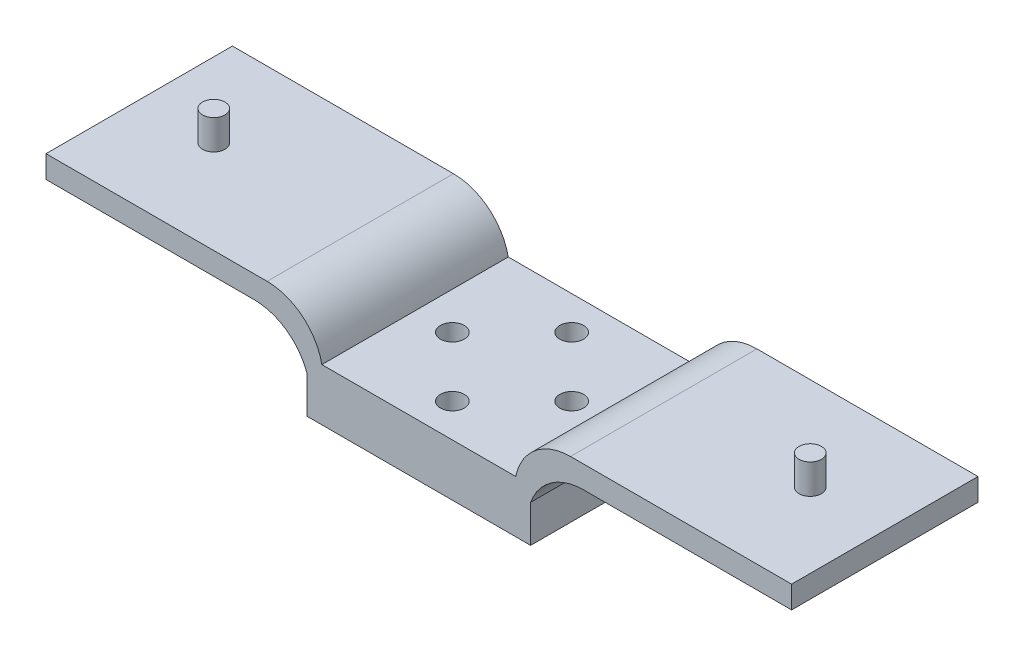
SolidWorks part; units mm, degrees
ref_plane "前视基准面" through (0, 0, 0) normal (0, 0, 1) x (1, 0, 0)
ref_plane "上视基准面" through (0, 0, 0) normal (0, 1, 0) x (1, 0, 0)
ref_plane "右视基准面" through (0, 0, 0) normal (1, 0, 0) x (0, 0, -1)
sketch "Sketch1" plane through (0, 0, 0) normal (0, 1, 0) x (1, 0, 0)
  line L1 (-50, 12.5) -> (50, 12.5)
  line L2 (-50, 12.5) -> (-50, -12.5)
  line L3 (-50, -12.5) -> (50, -12.5)
  line L4 (50, 12.5) -> (50, -12.5)
  line L5 (0, -12.5) -> (0, 12.5) construction
  line L6 (-50, 0) -> (50, 0) construction
  point P0 (0, 0)
  dimension "D1" = 100
  dimension "D2" = 25
extrude "Boss-Extrude1" add sketch "Sketch1" along normal blind 3
sketch "Sketch2" plane through (0, 0, 0) normal (0, -1, 0) x (1, 0, 0)
  line L0 (50, -12.5) -> (-50, -12.5) construction
  line L1 (-15, 12.5) -> (15, 12.5)
  line L2 (-15, 12.5) -> (-15, -12.5)
  line L3 (-15, -12.5) -> (15, -12.5)
  line L4 (15, 12.5) -> (15, -12.5)
  line L5 (0, -12.5) -> (0, 12.5) construction
  line L6 (-15, 0) -> (15, 0) construction
  point P0 (0, 0)
  dimension "D1" = 30
extrude "Boss-Extrude2" add sketch "Sketch2" along normal blind 5
sketch "Sketch3" plane through (0, 3, 0) normal (0, 1, 0) x (1, 0, 0)
  line L0 (-50, -12.5) -> (50, -12.5) construction
  line L1 (-9.5, 9.5) -> (9.5, 9.5)
  line L2 (-9.5, 9.5) -> (-9.5, -9.5)
  line L3 (-9.5, -9.5) -> (9.5, -9.5)
  line L4 (9.5, 9.5) -> (9.5, -9.5)
  line L5 (0, -9.5) -> (0, 9.5) construction
  line L6 (-9.5, 0) -> (9.5, 0) construction
  point P0 (0, 0)
  dimension "D1" = 3
extrude "Cut-Extrude1" [suppressed] cut sketch "Sketch3" against normal offset from surface (7 mm away) 2
sketch "Sketch5" plane through (0, -5, 0) normal (0, -1, 0) x (1, 0, 0)
  circle A0 centre (8, 0) radius 1.6
  circle A1 centre (0, -8) radius 1.6
  circle A2 centre (-8, 0) radius 1.6
  circle A3 centre (0, 8) radius 1.6
  point P2 (0, 0)
  point P12 (0, 0)
  dimension "D1" = 3.2
  dimension "D2" = 8
  dimension "D3" = 4
extrude "Cut-Extrude2" cut sketch "Sketch5" against normal through all
sketch "Sketch6" plane through (0, 0, -12.5) normal (0, 0, -1) x (-1, 0, 0)
  line L0 (-13, 3) -> (-13, -3)
  line L1 (-50, 3) -> (50, 3) construction
  line L2 (-13, -3) -> (13, -3)
  line L3 (13, -3) -> (13, 3)
  line L4 (13, 3) -> (-13, 3)
  line L5 (15, -5) -> (-15, -5) construction
  line L6 (15, -5) -> (15, 0) construction
  line L7 (-15, -5) -> (-15, 0) construction
  dimension "D1" = 2
  dimension "D2" = 2
  dimension "D3" = 2
extrude "Cut-Extrude3" cut sketch "Sketch6" against normal through all
fillet "Fillet1" radius 7.5 4 edges at (-15, 0, 0) (15, 0, 0) (-13, 3, 0) (13, 3, 0)
sketch "Sketch7" plane through (0, 3, 0) normal (0, 1, 0) x (1, 0, 0)
  line L0 (0, 0) -> (0, -25.2745) construction
  circle A0 centre (-40, 0) radius 1.5
  circle A1 centre (40, 0) radius 1.5
  point P7 (0, 0)
  dimension "D1" = 3
  dimension "D2" = 40
extrude "Boss-Extrude3" add sketch "Sketch7" along normal blind 4
sketch "Sketch8" plane through (0, -5, 0) normal (0, -1, 0) x (1, 0, 0)
  line L0 (-15, 12.5) -> (15, -12.5)
  circle A0 centre (0, 0) radius 5.5214
sketch "Sketch9" plane through (0, -5, 0) normal (0, -1, 0) x (1, 0, 0)
  line L4 (15, -12.5) -> (15, 12.5)
  line L5 (15, 12.5) -> (-15, 12.5)
  line L6 (-15, 12.5) -> (-15, -12.5)
  line L7 (-15, -12.5) -> (15, -12.5)
  line L8 (15, -12.5) -> (15, 12.5)
  line L9 (15, 12.5) -> (-15, 12.5)
  line L10 (-15, 12.5) -> (-15, -12.5)
  line L11 (-15, -12.5) -> (15, -12.5)
  circle A1 centre (0, -8) radius 1.6 construction
  circle A2 centre (-8, 0) radius 1.6 construction
  circle A3 centre (8, 0) radius 1.6 construction
  circle A4 centre (0, 8) radius 1.6 construction
  circle A5 centre (0, -8) radius 1.6
  circle A6 centre (-8, 0) radius 1.6
  circle A7 centre (8, 0) radius 1.6
  circle A8 centre (0, 8) radius 1.6
  dimension "D1" = 0
extrude "Boss-Extrude4" add sketch "Sketch9" along normal blind 5
